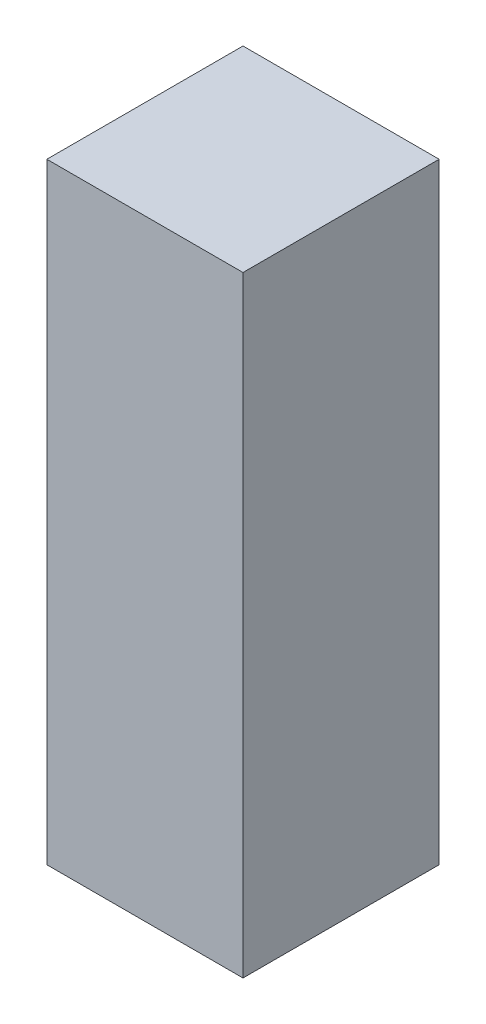
SolidWorks part; units mm, degrees
ref_plane "Front Plane" through (0, 0, 0) normal (0, 0, 1) x (1, 0, 0)
ref_plane "Top Plane" through (0, 0, 0) normal (0, 1, 0) x (1, 0, 0)
ref_plane "Right Plane" through (0, 0, 0) normal (1, 0, 0) x (0, 0, -1)
sketch "Sketch1" plane through (0, 0, 0) normal (0, 1, 0) x (1, 0, 0)
  line L1 (0, 0) -> (25.4, 0)
  line L2 (0, 0) -> (0, 25.4)
  line L3 (0, 25.4) -> (25.4, 25.4)
  line L4 (25.4, 0) -> (25.4, 25.4)
  dimension "D1" = 25.4
  dimension "D2" = 25.4
extrude "Boss-Extrude1" add sketch "Sketch1" along normal blind 387.096
sketch "Sketch2" plane through (0, 387.096, 0) normal (0, 1, 0) x (1, 0, 0)
  line L1 (0, 25.4) -> (25.4, 25.4)
  line L2 (0, 25.4) -> (0, 0)
  line L3 (0, 0) -> (25.4, 0)
  line L4 (25.4, 25.4) -> (25.4, 0)
extrude "Cut-Extrude1" cut sketch "Sketch2" against normal blind 307.975
